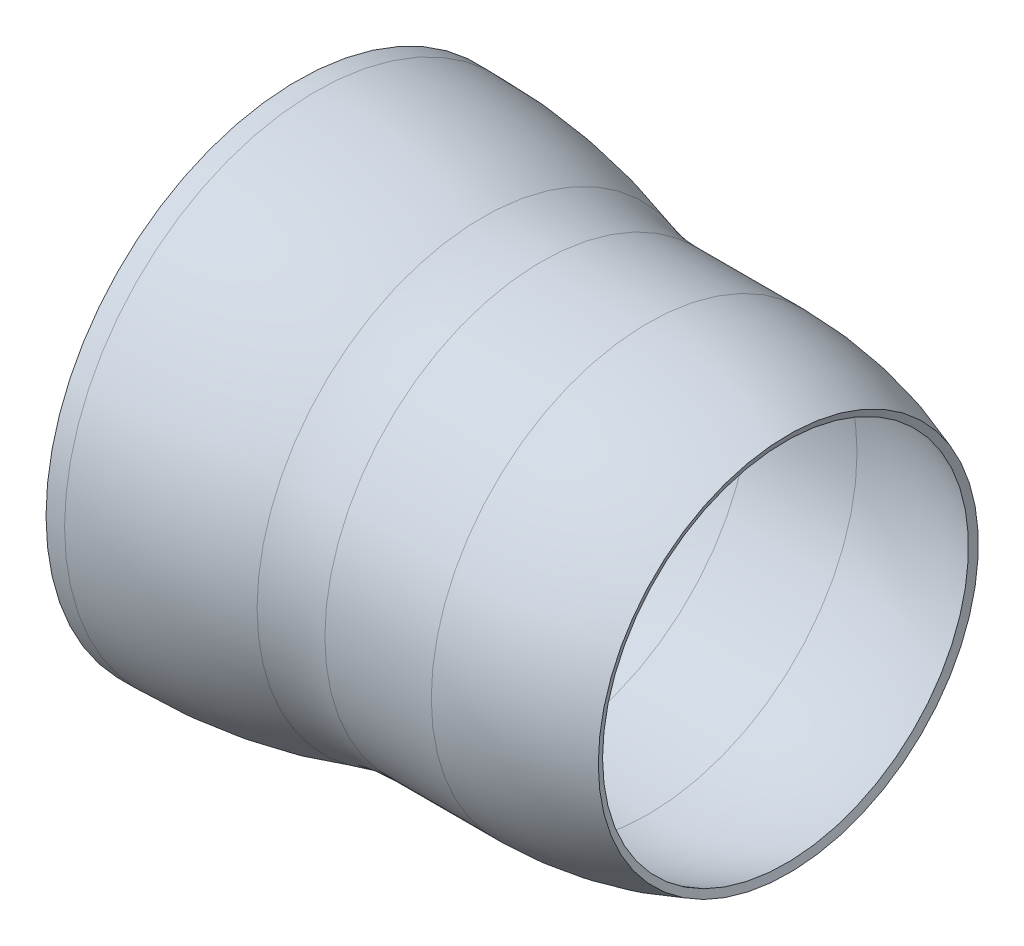
SolidWorks part; units mm, degrees
ref_plane "Front Plane" through (0, 0, 0) normal (0, 0, 1) x (1, 0, 0)
ref_plane "Top Plane" through (0, 0, 0) normal (0, 1, 0) x (1, 0, 0)
ref_plane "Right Plane" through (0, 0, 0) normal (1, 0, 0) x (0, 0, -1)
sketch "Sketch1" plane through (0, 0, 0) normal (0, 0, 1) x (1, 0, 0)
  line L0 (0, 0) -> (0, 160.5)
  line L1 (0, 160.5) -> (12.209, 160.5)
  line L2 (0, 0) -> (321, 0) construction
  line L3 (321, 0) -> (321, 120.375)
  line L5 (160.5, 137.5714) -> (230.5, 137.5714)
  line L6 (0, 165.5) -> (12.209, 165.5)
  line L7 (160.5, 142.5714) -> (230.5, 142.5714)
  line L8 (0, 165.5) -> (0, 160.5)
  line L9 (321, 120.375) -> (322.8339, 125.0265)
  arc A0 (12.209, 160.5) -> (120.375, 143.7755) centre (12.209, -197.6452) cw
  arc A2 (160.5, 137.5714) -> (120.375, 143.7755) centre (160.5, 270.4281) cw
  arc A3 (230.5, 137.5714) -> (321, 120.375) centre (230.5, -109.1649) cw
  arc A4 (12.209, 165.5) -> (121.8851, 148.542) centre (12.209, -197.6452) cw
  arc A5 (160.5, 142.5714) -> (121.8851, 148.542) centre (160.5, 270.4281) cw
  arc A6 (230.5, 142.5714) -> (322.8339, 125.0265) centre (230.5, -109.1649) cw
  dimension "D1" = 160.5
  dimension "D2" = 120.375
  dimension "D3" = 321
  dimension "D5" = 12.209
  dimension "D6" = 200.625
  dimension "D7" = 160.5
  dimension "D4" = 137.5714
  dimension "D8" = 70
  dimension "D9" = 5
revolve "Revolve1" add sketch "Sketch1" angle 360 about L2 region at (3.2597, 163, 0)
equation "\"ThrusterDim\"=160.5mm"
equation "\"D1@Sketch1\"=\"ThrusterDim\""
equation "\"D2@Sketch1\"=.75 * \"ThrusterDim\""
equation "\"D3@Sketch1\"=2 * \"ThrusterDim\""
equation "\"D6@Sketch1\"=\"ThrusterDim\" * 1.25"
equation "\"D7@Sketch1\"=\"ThrusterDim\""
equation "\"D4@Sketch1\"=\"ThrusterDim\"* 0.85714286"
equation "\"hatchHoleDiameter\"=600mm"
equation "\"hullThickness\"=177.1mm"
equation "\"gasketHullInterconnectWidth\"=100mm"
equation "\"collarThickness\"=20mm"
equation "\"hatchTunnelLength\"=200mm"
equation "\"oRingDiameter\"=2mm"
equation "\"boltPatternRadiusInterconnect\"=500mm"
equation "\"interconnectBoltDiameter\"=30mm"
equation "\"hatchShaftDiameter\"=20mm"
equation "\"hatchMinima\"=39.9mm"
equation "\"hullDiameter\"=2240mm"
equation "\"hatchMaxima\"=180mm"
equation "\"bushingFlatHatch\"=15mm"
equation "\"hingePivotDiameter\"=20mm"
equation "\"handleWidth\"=250mm"
equation "\"handleHeight\"=160mm"
equation "\"handleThickness\"=25mm"
equation "\"FrameLength\"=2600mm"
equation "\"FrameMidLength\"=1800mm"
equation "\"TubeOD\"=100mm"
equation "\"FrameBackFlat\"=500mm"
equation "\"TubeWall\"=15.0001mm"
equation "\"TopMemberAngle\"=140deg"
equation "\"FrameHight\"=2500mm"
